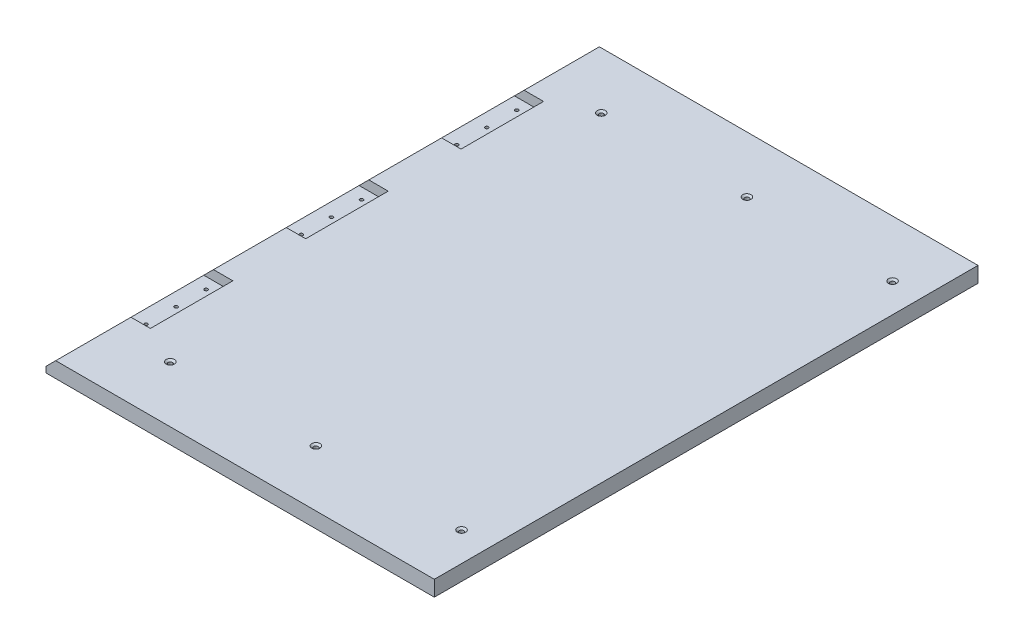
SolidWorks part; units mm, degrees
ref_plane "Front Plane" through (0, 0, 0) normal (0, 0, 1) x (1, 0, 0)
ref_plane "Top Plane" through (0, 0, 0) normal (0, 1, 0) x (1, 0, 0)
ref_plane "Right Plane" through (0, 0, 0) normal (1, 0, 0) x (0, 0, -1)
other "Bounding Box"
ref_plane "Default Plane" through (-200, 16, 280) normal (1, 0, 0) x (0, 0, -1)
sketch "Sketch1" plane through (0, 0, 0) normal (0, 1, 0) x (1, 0, 0)
  line L1 (-200, -280) -> (200, -280)
  line L2 (-200, -280) -> (-200, 280)
  line L3 (-200, 280) -> (200, 280)
  line L4 (200, -280) -> (200, 280)
  line L5 (-200, -280) -> (200, 280) construction
  line L6 (-200, 280) -> (200, -280) construction
  point P0 (0, 0)
  dimension "D1" = 560
  dimension "D2" = 400
extrude "Boss-Extrude1" add sketch "Sketch1" along normal blind 16 contours L2 L3 L4 L1
sketch "Sketch2" plane through (0, 16, 0) normal (0, 1, 0) x (1, 0, 0)
  line L0 (-200, 117.5) -> (-170, 117.5)
  line L1 (-200, 117.5) -> (-200, 202.5)
  line L2 (-200, 202.5) -> (-170, 202.5)
  line L3 (-170, 117.5) -> (-170, 202.5)
  line L4 (0, 0) -> (-170, 0) construction
  line L13 (-200, 280) -> (200, 280) construction
  line L14 (-200, -280) -> (-200, 280) construction
  line L15 (-200, -42.5) -> (-170, -42.5)
  line L16 (-200, -42.5) -> (-200, 42.5)
  line L17 (-200, 42.5) -> (-170, 42.5)
  line L18 (-170, -42.5) -> (-170, 42.5)
  line L19 (-200, -202.5) -> (-170, -202.5)
  line L20 (-200, -202.5) -> (-200, -117.5)
  line L21 (-200, -117.5) -> (-170, -117.5)
  line L22 (-170, -202.5) -> (-170, -117.5)
  point P4 (-170, 160)
  point P12 (-170, 0)
  dimension "D1" = 30
  dimension "D2" = 85
  dimension "D3" = 120
  dimension "D4" = 3
extrude "Cut-Extrude1" cut sketch "Sketch2" against normal blind 10
sketch "Sketch3" plane through (0, 0, 0) normal (0, -1, 0) x (1, 0, 0)
  line L0 (-200, -280) -> (200, -280) construction
  line L1 (-200, 280) -> (-160, 280)
  line L2 (-200, 280) -> (-200, -280)
  line L3 (-200, -280) -> (-160, -280)
  line L4 (-160, 280) -> (-160, -280)
  dimension "D1" = 40
extrude "Boss-Extrude2" [suppressed] add sketch "Sketch3" along normal blind 16
chamfer "Chamfer2" distance 10 angle 45 4 edges at (-200, 16, -241.25) (-200, 16, -80) (-200, 16, 80) (-200, 16, 241.25)
hole_wizard "#8-36 Tapped Hole1" positions "Sketch8" profile "Sketch7" tap size "#8-36" standard "ANSI Inch"
sketch "Sketch8" plane through (0, 6, 0) normal (0, 1, 0) x (1, 0, 0)
  line L0 (-186, -160) -> (-174.3637, -160) construction
  line L2 (-170, -202.5) -> (-170, -117.5) construction
  line L3 (-170, -117.5) -> (-190, -117.5) construction
  line L4 (-200, -202.5) -> (-170, -202.5) construction
  line L5 (-200, -280) -> (-200, -202.5) construction
  line L6 (-190, -280) -> (200, -280) construction
  line L7 (-200, -117.5) -> (-200, -202.5) construction
  point P0 (-186, -129)
  point P2 (-186, -160)
  point P4 (-186, -191)
  dimension "D1" = 16
  dimension "D2" = 62
sketch "Sketch7" plane through (-186, 6, 129) normal (1, 0, 0) x (0, 0, 1)
  line L0 (0, 0) -> (0, 26.0378)
  line L1 (0, 26.0378) -> (1.7272, 25)
  line L2 (1.7272, 25) -> (1.7272, 0)
  line L5 (1.7272, 0) -> (0, 0)
  line L10 (0, 26.0378) -> (-1.7272, 25) construction
  line L11 (0, -6.35) -> (0, 107.95) construction
  dimension "Tap Drill Dia." = 3.4544
  dimension "Tap Drill Depth" = 25
  dimension "Drill Angle" = 118
cosmetic thread "Hole Thread1" parameters "D1"=20, "D2"=4.1656
cosmetic thread "Hole Thread2" parameters "D1"=20, "D2"=4.1656
cosmetic thread "Hole Thread3" parameters "D1"=20, "D2"=4.1656
pattern_linear "LPattern1" count 3 spacing 160 along (0, 0, -1) of "#8-36 Tapped Hole1"
cosmetic thread "Hole Thread4" parameters "D1"=20, "D2"=4.1656
cosmetic thread "Hole Thread5" parameters "D1"=20, "D2"=4.1656
cosmetic thread "Hole Thread6" parameters "D1"=20, "D2"=4.1656
cosmetic thread "Hole Thread7" parameters "D1"=20, "D2"=4.1656
cosmetic thread "Hole Thread8" parameters "D1"=20, "D2"=4.1656
cosmetic thread "Hole Thread9" parameters "D1"=20, "D2"=4.1656
hole_wizard "CSK for #8 Flat Head Machine Screw (100)1" positions "Sketch9" profile "Sketch10" countersink size "#8" standard "ANSI Inch" end condition through all
sketch "Sketch9" plane through (617.7049, 16, 0) normal (0, 1, 0) x (1, 0, 0)
  line L1 (-447.7049, -222) -> (-747.7049, -222) construction
  line L6 (-597.7049, -222) -> (-597.7049, -129.5989) construction
  point P0 (-447.7049, -222)
  point P1 (-597.7049, -222)
  point P2 (-747.7049, -222)
sketch "Sketch10" plane through (170, 16, 222) normal (1, 0, 0) x (0, 0, 1)
  line L0 (0, 0) -> (0, 16)
  line L1 (0, 16) -> (2.2479, 16)
  line L2 (2.2479, 16) -> (2.2479, 1.6518)
  line L3 (2.2479, 1.6518) -> (4.2164, 0)
  line L5 (4.2164, 0) -> (0, 0)
  line L6 (-2.2479, 1.6518) -> (-4.2164, 0) construction
  line L11 (0, -6.35) -> (0, 107.95) construction
  dimension "Thru Hole Dia." = 4.4958
  dimension "Thru Hole Depth" = 16
  dimension "Near C'Sink Dia." = 8.4328
  dimension "Near C'Sink Angle" = 100
mirror "Mirror1" about plane through (0, 0, 0) normal (0, 0, 1) of "CSK for #8 Flat Head Machine Screw (100)1"
sketch "Sketch11" plane through (0, 16, 0) normal (0, 1, 0) x (1, 0, 0)
  line L0 (-190, -280) -> (200, -280) construction
  line L1 (200, 280) -> (184, 280)
  line L2 (200, 280) -> (200, -280)
  line L3 (200, -280) -> (184, -280)
  line L4 (184, 280) -> (184, -280)
  dimension "D1" = 16
extrude "Boss-Extrude3" [suppressed] add sketch "Sketch11" along normal blind 25
fillet "Fillet1" [suppressed] radius 8
